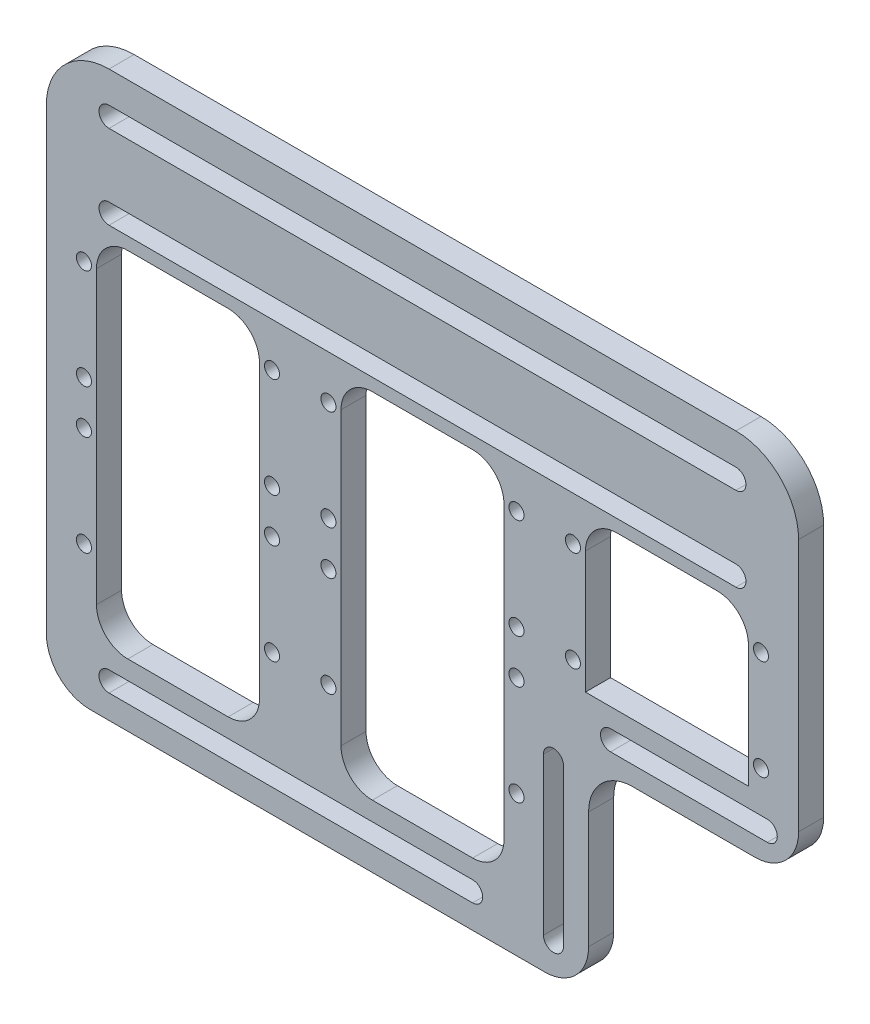
SolidWorks part; units mm, degrees
material "PET"
ref_plane "Front Plane" through (0, 0, 0) normal (0, 0, 1) x (1, 0, 0)
ref_plane "Top Plane" through (0, 0, 0) normal (0, 1, 0) x (1, 0, 0)
ref_plane "Right Plane" through (0, 0, 0) normal (1, 0, 0) x (0, 0, -1)
sketch "Sketch1" plane through (0, 0, 0) normal (0, 0, 1) x (1, 0, 0)
  line L1 (60, -45) -> (-60, -45)
  line L2 (60, -45) -> (60, 45)
  line L3 (60, 45) -> (-60, 45)
  line L4 (-60, -45) -> (-60, 45)
  line L5 (60, -45) -> (-60, 45) construction
  line L6 (60, 45) -> (-60, -45) construction
  point P0 (0, 0)
  dimension "D1" = 120
  dimension "D2" = 90
extrude "plate" add sketch "Sketch1" along normal blind 4
sketch "Sketch2" plane through (0, 0, 4) normal (0, 0, 1) x (1, 0, 0)
  line L0 (50, 38.4) -> (-50, 38.4) construction
  line L1 (50, 36.8) -> (-50, 36.8)
  line L2 (50, 40) -> (-50, 40)
  line L3 (60, 45) -> (-60, 45) construction
  line L4 (-60, 45) -> (-60, -45) construction
  arc A0 (50, 36.8) -> (50, 40) centre (50, 38.4) ccw
  arc A1 (-50, 40) -> (-50, 36.8) centre (-50, 38.4) ccw
  point P2 (0, 38.4)
  dimension "D1" = 1.6
  dimension "D2" = 5
  dimension "D3" = 10
extrude "slot_cut" cut sketch "Sketch2" against normal through all
pattern_linear "second_slot" count 2 spacing 13.38 along (0, -1, 0) of "slot_cut"
sketch "motor_outline" plane through (0, 0, 4) normal (0, 0, 1) x (1, 0, 0)
  line L0 (18.75, -1.58) -> (18.75, 18.42)
  line L1 (-20.25, -1.58) -> (-57.75, -1.58)
  line L2 (-20.25, -1.58) -> (-20.25, 18.42)
  line L3 (-20.25, 18.42) -> (-57.75, 18.42)
  line L4 (-57.75, -1.58) -> (-57.75, 18.42)
  line L5 (-20.25, -1.58) -> (-57.75, 18.42) construction
  line L6 (-20.25, 18.42) -> (-57.75, -1.58) construction
  line L7 (18.75, -1.58) -> (-18.75, -1.58)
  line L8 (-18.75, -1.58) -> (-18.75, 18.42)
  line L9 (18.75, 18.42) -> (-18.75, 18.42)
  line L10 (57.75, -1.58) -> (57.75, 18.42)
  line L11 (57.75, -1.58) -> (20.25, -1.58)
  line L12 (20.25, -1.58) -> (20.25, 18.42)
  line L13 (57.75, 18.42) -> (20.25, 18.42)
  line L14 (-18.75, 18.42) -> (18.75, -1.58) construction
  line L15 (18.75, 18.42) -> (-18.75, -1.58) construction
  line L16 (-50, 23.42) -> (50, 23.42) construction
  line L17 (-39, 8.42) -> (-39, 18.42) construction
  line L18 (-39, 8.42) -> (-57.75, 8.42) construction
  line L19 (-52, 16.42) -> (-52, -30)
  line L24 (-47, -35) -> (-31, -35)
  line L25 (-26, -30) -> (-26, 16.42)
  line L26 (-31, 21.42) -> (-47, 21.42)
  line L27 (-60, -45) -> (60, -45) construction
  circle A0 centre (-54, 16.42) radius 1.2
  circle A1 centre (-54, 0.42) radius 1.2
  circle A2 centre (-24, 0.42) radius 1.2
  circle A3 centre (-24, 16.42) radius 1.2
  arc A4 (-52, -30) -> (-47, -35) centre (-47, -30) ccw
  arc A5 (-31, -35) -> (-26, -30) centre (-31, -30) ccw
  arc A6 (-26, 16.42) -> (-31, 21.42) centre (-31, 16.42) ccw
  arc A7 (-52, 16.42) -> (-47, 21.42) centre (-47, 16.42) cw
  point P0 (-39, 8.42)
  point P6 (0, 8.42)
  dimension "D6" = 2.4
  dimension "D11" = 5
  dimension "D2" = 20
  dimension "D4" = 5
  dimension "D5" = 39
  dimension "D7" = 16
  dimension "D1" = 30
  dimension "D8" = 2
  dimension "D9" = 10
  dimension "D10" = 2
  dimension "D3" = 3
extrude "motor_mount" cut sketch "motor_outline" against normal through all contours A0 | A3 | A2 | A1
pattern_linear "motors" count 3 spacing 39 along (1, 0, 0) count 2 spacing 23 along (0, -1, 0) of "motor_mount"
extrude "motor_cutout" cut sketch "motor_outline<5>" against normal through all contours L24 A5 L25 L1 L19 A4 | A7 L19 L1 L25 A6 L3 | A7 L3 A6 L26 region at (-39, -18.095, 4) region at (-39, 8.41, 4) region at (-39, 19.8433, 4)
sketch "motor_outline<5>" plane through (0, 0, 4) normal (0, 0, 1) x (1, 0, 0) same geometry as "motor_outline"
pattern_linear "cutout_pattern" count 3 spacing 39 along (1, 0, 0) of "motor_cutout"
fillet "Fillet1" radius 10 2 edges at (60, 45, 2) (-60, 45, 2)
sketch "Sketch4" plane through (0, 0, 4) normal (0, 0, 1) x (1, 0, 0)
  line L0 (-24, 16.42) -> (-15, 16.42) construction
  line L1 (-24, -22.58) -> (-15, -22.58) construction
  line L2 (-19.5, 16.42) -> (-19.5, -22.58) construction
  line L3 (-17.5, 16.42) -> (-17.5, -22.58)
  line L4 (-21.5, 16.42) -> (-21.5, -22.58)
  circle A0 centre (-15, 16.42) radius 1.2 construction
  circle A1 centre (-24, 16.42) radius 1.2 construction
  circle A2 centre (-15, 16.42) radius 1.2 construction
  circle A3 centre (-24, 16.42) radius 1.2 construction
  arc A4 (-17.5, 16.42) -> (-21.5, 16.42) centre (-19.5, 16.42) ccw
  arc A5 (-21.5, -22.58) -> (-17.5, -22.58) centre (-19.5, -22.58) ccw
  point P6 (-19.5, 16.42)
  point P10 (-19.5, -22.58)
  point P11 (-19.5, -3.08)
  dimension "D1" = 2
sketch "Sketch5" plane through (0, 0, 4) normal (0, 0, 1) x (1, 0, 0)
  line L0 (24, 0.42) -> (24, -6.58) construction
  line L1 (24, -3.08) -> (52, -3.08)
  line L2 (52, -30) -> (52, 16.42) construction
  line L5 (24, -5.38) -> (24, -3.08)
  line L6 (24, -5.38) -> (52, -5.38)
  line L7 (52, -5.38) -> (52, -3.08)
  circle A0 centre (24, -6.58) radius 1.2 construction
  point P0 (24, 0.42)
  point P1 (24, -6.58)
extrude "Boss-Extrude1" add sketch "Sketch5" against normal up to surface (4 mm away) up to face at (0, -6.79, 0)
sketch "Sketch6" plane through (0, 0, 4) normal (0, 0, 1) x (1, 0, 0)
  line L0 (15, -22.58) -> (24, -22.58) construction
  line L2 (26, -5.38) -> (52, -5.38) construction
  line L3 (26, -5.38) -> (52, -5.38) construction
  line L5 (60, -5.38) -> (19.5, -5.38)
  line L6 (60, -45) -> (60, 35) construction
  line L7 (19.5, -5.38) -> (19.5, -45)
  line L8 (-60, -45) -> (60, -45) construction
  line L9 (60, -5.38) -> (60, -45)
  line L10 (60, -45) -> (19.5, -45)
  point P0 (15, -22.58)
  point P1 (24, -22.58)
  point P17 (19.5, -22.58)
extrude "Cut-Extrude1" cut sketch "Sketch6" against normal through all
sketch "Sketch7" plane through (0, 0, 4) normal (0, 0, 1) x (1, 0, 0)
  line L0 (-50, -39.6) -> (8, -39.6) construction
  line L1 (-50, -38) -> (8, -38)
  line L2 (-50, -41.2) -> (8, -41.2)
  line L3 (-60, 35) -> (-60, -45) construction
  line L4 (-47, -35) -> (-31, -35) construction
  arc A0 (-50, -38) -> (-50, -41.2) centre (-50, -39.6) ccw
  arc A1 (8, -41.2) -> (8, -38) centre (8, -39.6) ccw
  point P2 (-21, -39.6)
  dimension "D2" = 1.6
  dimension "D1" = 58
  dimension "D3" = 10
  dimension "D4" = 3
extrude "U2D2_mount" cut sketch "Sketch7" against normal through all
sketch "Sketch8" plane through (0, 0, 4) normal (0, 0, 1) x (1, 0, 0)
  line L0 (19.5, -5.38) -> (60, -5.38) construction
  line L1 (19.5, -5.38) -> (19.5, -45) construction
  line L2 (19.5, -5.38) -> (60, -5.38)
  line L3 (19.5, -5.38) -> (19.5, -45)
  line L4 (26.5, -12.38) -> (60, -12.38)
  line L5 (26.5, -12.38) -> (26.5, -45)
  line L6 (60, -12.38) -> (60, -5.38)
  line L7 (26.5, -45) -> (19.5, -45)
  dimension "D1" = 7
extrude "Boss-Extrude2" add sketch "Sketch8" against normal up to surface (4 mm away) up to face at (-21, -39.6, 0)
sketch "Sketch9" plane through (0, 0, 4) normal (0, 0, 1) x (1, 0, 0)
  line L0 (30, -7.73) -> (55, -7.73) construction
  line L1 (30, -6.13) -> (55, -6.13)
  line L2 (30, -9.33) -> (55, -9.33)
  line L3 (20.9, -15) -> (20.9, -40) construction
  line L4 (22.5, -15) -> (22.5, -40)
  line L5 (19.3, -15) -> (19.3, -40)
  line L6 (52, -3.08) -> (26, -3.08) construction
  line L7 (26.5, -12.38) -> (60, -12.38) construction
  line L9 (-60, -45) -> (26.5, -45) construction
  line L10 (26.5, -45) -> (26.5, -12.38) construction
  line L11 (26.5, -45) -> (26.5, -12.38) construction
  line L12 (60, -12.38) -> (60, 35) construction
  arc A0 (30, -6.13) -> (30, -9.33) centre (30, -7.73) ccw
  arc A1 (55, -9.33) -> (55, -6.13) centre (55, -7.73) ccw
  arc A2 (22.5, -15) -> (19.3, -15) centre (20.9, -15) ccw
  arc A3 (19.3, -40) -> (22.5, -40) centre (20.9, -40) ccw
  point P2 (42.5, -7.73)
  point P7 (20.9, -27.5)
  point P28 (0, 0)
  point P30 (22.003, -45)
  dimension "D1" = 1.6
  dimension "D2" = 1.6
  dimension "D3" = 5
  dimension "D4" = 25
  dimension "D5" = 5
  dimension "D6" = 25
  dimension "D7" = 4
extrude "thumb_mount" cut sketch "Sketch9" against normal through all
fillet "Fillet3" radius 7 4 edges at (-60, -45, 2) (26.5, -45, 2) (60, -12.38, 2) (26.5, -12.38, 2)
equation "\"d\"= 10'distance from slot to the side"
equation "\"D3@Sketch2\"=\"d\""
equation "\"a\"= 120'palm size"
equation "\"D1@Sketch1\"=\"a\""
equation "\"spacing\"= 39'for linear patterns"
equation "\"D5@motor_outline\"=\"spacing\""
equation "\"D3@motors\"=\"spacing\""
equation "\"D3@cutout_pattern\"=\"spacing\""
equation "\"D3@LPattern6\"=\"spacing\""
